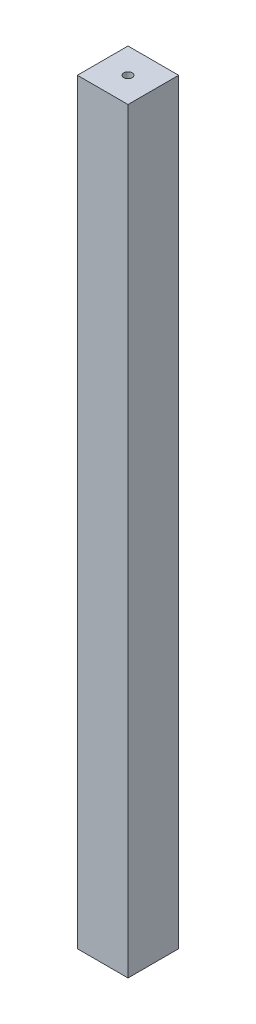
SolidWorks part; units mm, degrees
ref_plane "Front Plane" through (0, 0, 0) normal (0, 0, 1) x (1, 0, 0)
ref_plane "Top Plane" through (0, 0, 0) normal (0, 1, 0) x (1, 0, 0)
ref_plane "Right Plane" through (0, 0, 0) normal (1, 0, 0) x (0, 0, -1)
sketch "Sketch1" plane through (0, 0, 0) normal (0, 1, 0) x (1, 0, 0)
  line L1 (0, 0) -> (15, 0)
  line L2 (0, 0) -> (0, 15)
  line L3 (0, 15) -> (15, 15)
  line L4 (15, 0) -> (15, 15)
  dimension "D1" = 15
  dimension "15" = 15
extrude "Boss-Extrude1" add sketch "Sketch1" along normal blind 224
sketch "Sketch2" plane through (0, 224, 0) normal (0, 1, 0) x (1, 0, 0)
  line L0 (0, 15) -> (15, 0) construction
  circle A0 centre (7.5, 7.5) radius 1.25
  point P6 (7.5, 7.5)
  dimension "D1" = 2.5
extrude "Cut-Extrude1" cut sketch "Sketch2" against normal through all
